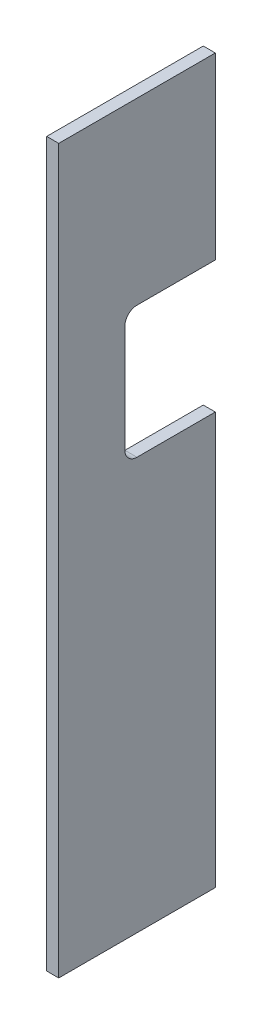
SolidWorks part; units mm, degrees
ref_plane "Plan de face" through (0, 0, 0) normal (0, 0, 1) x (1, 0, 0)
ref_plane "Plan de dessus" through (0, 0, 0) normal (0, 1, 0) x (1, 0, 0)
ref_plane "Plan de droite" through (0, 0, 0) normal (1, 0, 0) x (0, 0, -1)
sketch "Esquisse1" plane through (0, 0, 0) normal (0, 0, 1) x (1, 0, 0)
  line L0 (-109.309, 0) -> (-222.1354, 0) construction
  line L1 (-155.642, 600) -> (-165.642, 600)
  line L2 (-155.642, 600) -> (-155.642, 0)
  line L3 (-155.642, 0) -> (-165.642, 0)
  line L4 (-165.642, 600) -> (-165.642, 0)
  dimension "D1" = 10
extrude "Boss.-Extru.1" add sketch "Esquisse1" along normal up to surface (129.974 mm away)
sketch "Esquisse2" plane through (-155.642, 0, 0) normal (1, 0, 0) x (0, 0, -1)
  line L0 (0, 0) -> (0, 600) construction
  line L1 (0, 451.1811) -> (-65.046, 451.1811)
  line L2 (0, 451.1811) -> (0, 341.8976)
  line L3 (0, 341.8976) -> (-65.046, 341.8976)
  line L4 (-75.046, 441.1811) -> (-75.046, 351.8976)
  arc A0 (-65.046, 341.8976) -> (-75.046, 351.8976) centre (-65.046, 351.8976) cw
  arc A1 (-75.046, 441.1811) -> (-65.046, 451.1811) centre (-65.046, 441.1811) cw
  dimension "D1" = 10
extrude "Enlèv. mat.-Extru.1" cut sketch "Esquisse2" against normal blind 10
